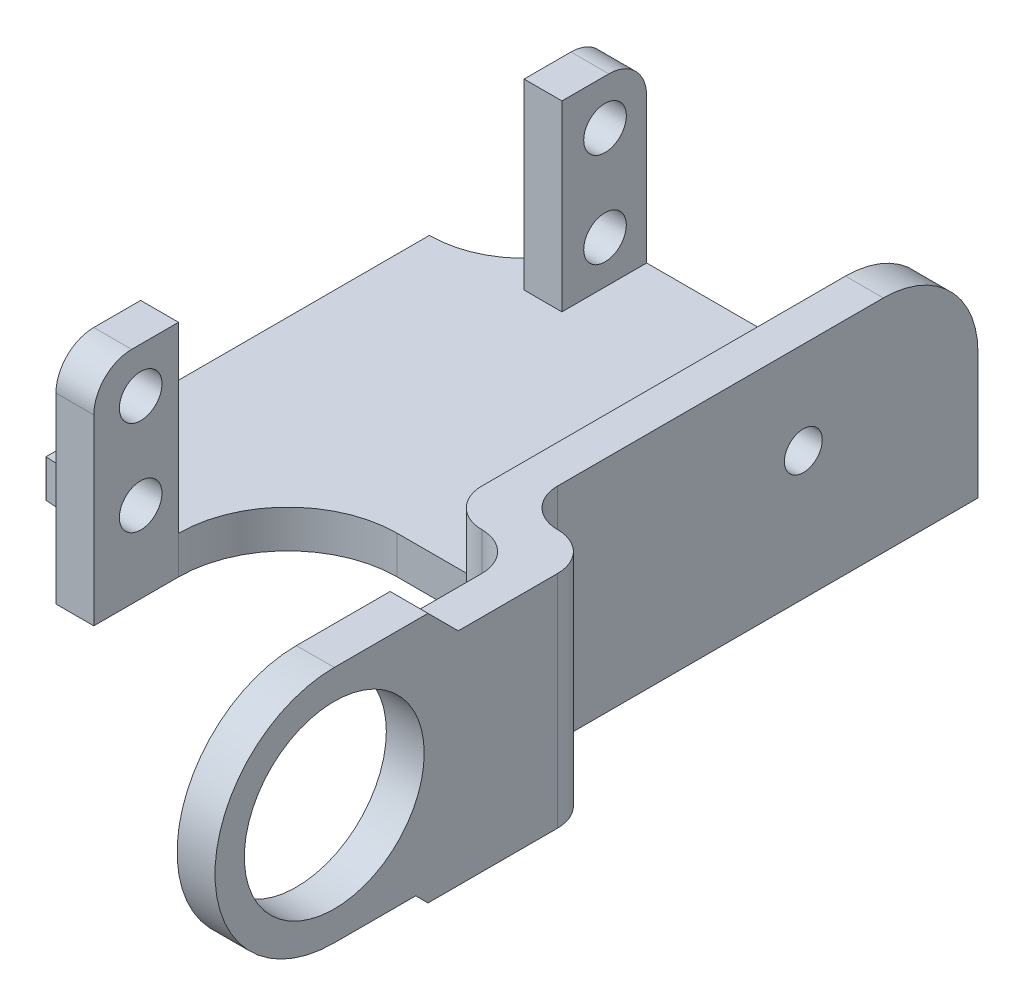
SolidWorks part; units mm, degrees
material "PLA"
ref_plane "Front Plane" through (0, 0, 0) normal (0, 0, 1) x (1, 0, 0)
ref_plane "Top Plane" through (0, 0, 0) normal (0, 1, 0) x (1, 0, 0)
ref_plane "Right Plane" through (0, 0, 0) normal (1, 0, 0) x (0, 0, -1)
sketch "Sketch1" plane through (0, 0, 0) normal (0, 1, 0) x (1, 0, 0)
  line L0 (-49, 49.45) -> (-39, 49.45)
  line L1 (-39, 49.45) -> (-39, 58.4)
  line L2 (-39, 58.4) -> (0, 58.4)
  line L3 (0, 58.4) -> (0, 0)
  line L4 (0, 0) -> (-39, 0)
  line L5 (-39, 0) -> (-39, 8.95)
  line L6 (-39, 8.95) -> (-49, 8.95)
  line L7 (-49, 8.95) -> (-49, 49.45)
  dimension "D1" = 58.4
  dimension "D2" = 49
  dimension "D3" = 10
  dimension "D4" = 8.95
  dimension "D5" = 8.95
extrude "Boss-Extrude1" add sketch "Sketch1" along normal blind 4
sketch "Sketch2" plane through (-39, 0, 0) normal (-1, 0, 0) x (0, 0, 1)
  line L0 (-58.4, 4) -> (-49.45, 4) construction
  line L1 (-8.95, 23.3) -> (0, 23.3)
  line L2 (-8.95, 23.3) -> (-8.95, 4)
  line L3 (-8.95, 4) -> (0, 4)
  line L4 (0, 23.3) -> (0, 4)
  line L5 (-58.4, 23.3) -> (-49.45, 23.3)
  line L6 (-58.4, 23.3) -> (-58.4, 4)
  line L7 (-58.4, 4) -> (-49.45, 4)
  line L8 (-49.45, 23.3) -> (-49.45, 4)
  line L9 (-58.4, 4) -> (-58.4, 0) construction
  line L10 (-49.45, 4) -> (-49.45, 0) construction
  line L11 (-8.95, 4) -> (0, 4) construction
  line L12 (0, 4) -> (0, 0) construction
  line L13 (-8.95, 4) -> (-8.95, 0) construction
  line L14 (-49.45, 4) -> (-8.95, 4) construction
  line L15 (-54, 18.55) -> (-54, 8.55) construction
  circle A0 centre (-4.95, 18.55) radius 2.25
  circle A1 centre (-4.95, 8.55) radius 2.25
  circle A2 centre (-54, 18.55) radius 2.25
  circle A3 centre (-54, 8.55) radius 2.25
  dimension "D1" = 4.5
  dimension "D2" = 4.5
  dimension "D8" = 4.5
  dimension "D9" = 4.5
  dimension "D3" = 19.3
  dimension "D4" = 10
  dimension "D5" = 4.55
  dimension "D6" = 4.55
  dimension "D7" = 4.55
  dimension "D10" = 4
extrude "Boss-Extrude2" add sketch "Sketch2" against normal blind 4
fillet "Fillet1" radius 10 2 edges at (-39, 2, -49.45) (-39, 2, -8.95)
fillet "Fillet2" radius 4 2 edges at (-37, 23.3, -58.4) (-37, 23.3, 0)
sketch "Sketch3" plane through (0, 0, 0) normal (1, 0, 0) x (0, 0, -1)
  line L0 (0, 4) -> (58.4, 4) construction
  line L1 (6, 23.3) -> (58.4, 23.3)
  line L2 (6, 23.3) -> (6, 4)
  line L3 (6, 4) -> (58.4, 4)
  line L4 (58.4, 23.3) -> (58.4, 4)
  line L6 (58.4, 4) -> (58.4, 0) construction
  circle A0 centre (39.95, 13.55) radius 2
  dimension "D4" = 4
  dimension "D1" = 19.3
  dimension "D2" = 18.45
  dimension "D3" = 9.55
  dimension "D5" = 52.4
extrude "Boss-Extrude3" add sketch "Sketch3" against normal blind 4
fillet "Fillet3" radius 10 1 edges at (-2, 23.3, -58.4)
sketch "Sketch4" plane through (0, 4, 0) normal (0, 1, 0) x (1, 0, 0)
  line L0 (-35, 0) -> (0, 0) construction
  line L1 (-35, 20.5) -> (-4, 20.5)
  line L2 (-35, 20.5) -> (-35, 0)
  line L3 (-35, 0) -> (-4, 0)
  line L4 (-4, 20.5) -> (-4, 0)
  line L5 (-35, 4) -> (-35, 8.95) construction
  line L6 (-4, 48.4) -> (-4, 6) construction
  dimension "D1" = 20.5
extrude "Cut-Extrude1" cut sketch "Sketch4" against normal blind 10
sketch "Sketch5" plane through (0, 4, 0) normal (0, 1, 0) x (1, 0, 0)
  line L4 (0, 6) -> (-4, 6)
  line L5 (-4, 6) -> (-4, 0)
  line L6 (-4, 0) -> (0, 0)
  line L7 (0, 0) -> (0, 6)
  line L8 (0, 6) -> (-4, 6)
  line L9 (-4, 6) -> (-4, 0)
  line L10 (-4, 0) -> (0, 0)
  line L11 (0, 0) -> (0, 6)
  dimension "D1" = 0
extrude "Cut-Extrude2" cut sketch "Sketch5" against normal blind 10
fillet "Fillet4" radius 11.55 1 edges at (-35, 2, -20.5)
sketch "Sketch6" plane through (0, 23.3, 0) normal (0, 1, 0) x (1, 0, 0)
  line L0 (-4, 6) -> (0, 6) construction
  line L1 (0, 10) -> (4, 10)
  line L2 (0, 10) -> (0, 6)
  line L3 (0, 6) -> (4, 6)
  line L4 (4, 10) -> (4, 6)
  line L5 (0, 48.4) -> (0, 6) construction
  dimension "D1" = 4
  dimension "D2" = 4
extrude "Boss-Extrude4" add sketch "Sketch6" against normal up to surface (23.3 mm away) up to face at (-28.7921, 0, -22.9186)
sketch "Sketch7" plane through (4, 0, 0) normal (1, 0, 0) x (0, 0, -1)
  line L0 (-4.5, 23.3) -> (10, 23.3)
  line L1 (10, 23.3) -> (10, 0)
  line L2 (10, 0) -> (-7.7, 0)
  line L3 (10, 0) -> (10, 23.3) construction
  line L4 (6, 23.3) -> (10, 23.3) construction
  line L5 (6, 0) -> (10, 0) construction
  line L6 (-17.6, 26.5) -> (-7.7, 26.5)
  line L7 (-7.7, 26.5) -> (-4.5, 23.3)
  line L8 (-7.7, 0) -> (-9, 1.3)
  line L9 (-9, 1.3) -> (-17.6, 1.3)
  circle A0 centre (-17.6, 13.9) radius 9.5
  arc A1 (-17.6, 26.5) -> (-17.6, 1.3) centre (-17.6, 13.9) ccw
  dimension "D1" = 19
  dimension "D2" = 25.2
  dimension "D3" = 3.2
  dimension "D4" = 3.2
  dimension "D5" = 27.6
  dimension "D6" = 13.1
  dimension "D7" = 1.3
  dimension "D8" = 1.3
extrude "Boss-Extrude5" add sketch "Sketch7" along normal blind 4
fillet "Fillet5" radius 4 4 edges at (-4, 11.65, -6) (4, 11.65, -6) (0, 11.65, -10) (8, 11.65, -10)
